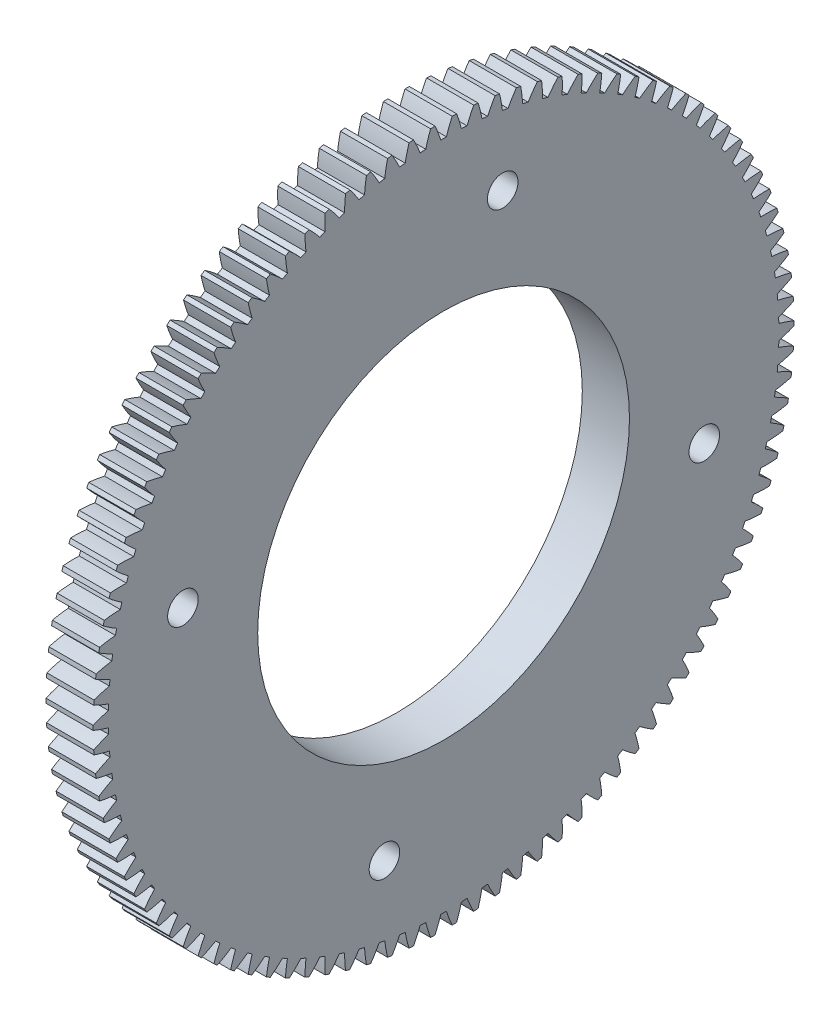
SolidWorks part; units mm, degrees
ref_plane "Plane1" through (0, 0, 0) normal (0, 0, 1) x (1, 0, 0)
ref_plane "Plane2" through (0, 0, 0) normal (0, 1, 0) x (1, 0, 0)
ref_plane "Plane3" through (0, 0, 0) normal (1, 0, 0) x (0, 0, -1)
sketch "HoldingSke" plane through (0, 0, 0) normal (0, 1, 0) x (1, 0, 0)
  line L0 (0, 0) -> (-105.6191, -496.899)
  line L1 (-15, 0) -> (100, 0) construction
  line L2 (0, 0) -> (-2.1039, 2.3779)
  line L3 (0, 0) -> (-11.863, 4.5341)
  line L4 (0, 0) -> (-1.7955, 8.4473)
  line L5 (0, 0) -> (-47.5972, -17.7524)
  line L6 (0, 0) -> (-7.3695, -4.9722)
  line L7 (-2.1039, 2.3779) -> (8.8308, 51.9871)
  line L8 (-76.2, 54.61) -> (-75.184, 54.61)
  line L9 (-71.009, 38.7566) -> (-53.1078, 45.2721)
  line L10 (-76.2, 71.12) -> (104.1128, 71.12)
  line L11 (0, 0) -> (-8.89, 0)
  line L12 (-76.2, 101.6) -> (-76.1492, 101.6)
  line L13 (24.9733, 27.94) -> (52.9518, 28.4284)
  line L14 (24.9733, 27.94) -> (25.0241, 27.9398)
  line L15 (24.9733, 27.94) -> (100.4021, 29.52)
  circle A0 centre (0, 0) radius 0.3969
  circle A1 centre (0, 0) radius 38.1
  circle A2 centre (0, 0) radius 38.1
  circle A3 centre (0, 0) radius 0.3969
  dimension "MHD" = 76.2
  dimension "Hub_dia" = 76.2
  dimension "Bore" = 0.7937
  dimension "MBD" = 0.7937
  dimension "Num_teeth" = 102
  dimension "Pitch" = 508
  dimension "Overall_len" = 50.8
  dimension "Show_teeth" = 102
  dimension "Thickness" = 8.89
  dimension "OAL" = 50.8001
  dimension "T_dim" = 1.016
  dimension "Ap" = 20
  dimension "H" = 19.05
  dimension "Pitch_radius" = 180.3128
  dimension "Width" = 8.89
  dimension "Backlash" = 0.0508
  dimension "Addendum_fac" = 1
  dimension "Dedendum_fac" = 1.2
  dimension "Clearance_fac" = 0.2
  dimension "Dedendum_add" = 0.0508
sketch "BasProSke" plane through (0, 0, 0) normal (0, 1, 0) x (1, 0, 0)
  line L0 (-10, 0) -> (60, 0) construction
  line L1 (0, 0) -> (0, 66.04)
  line L2 (0, 0) -> (8.89, 0)
  line L3 (8.89, 0) -> (8.89, 66.04)
  line L4 (8.89, 66.04) -> (0, 66.04)
  dimension "Thickness" = 8.89
  dimension "Diameter" = 132.08
revolve "Base-Revolve" add sketch "BasProSke" angle 360 about L0
sketch "TooCutSke" plane through (0, 0, 0) normal (1, 0, 0) x (0, 0, -1)
  line L1 (0, 0) -> (0, 107) construction
  line L2 (0, 0) -> (-1.0863, 64.7609) construction
  line L3 (0, 0) -> (-3.9888, 129.4658) construction
  line L4 (-1.0863, 64.7609) -> (-1.9944, 64.7329) construction
  arc A0 (0.5348, 63.1929) -> (-0.5348, 63.1929) centre (0, 0) ccw
  arc A1 (1.6252, 66.0454) -> (-1.6252, 66.0454) centre (0, 0) ccw
  circle A2 centre (0, 0) radius 64.77 construction
  circle A3 centre (0, 0) radius 60.8639 construction
  arc A4 (-0.5348, 63.1929) -> (-1.6252, 66.0454) centre (-25.2381, 55.3846) ccw
  arc A5 (1.6252, 66.0454) -> (0.5348, 63.1929) centre (25.2381, 55.3846) ccw
  dimension "Root_dia" = 126.3904
  dimension "Overcut_dia" = 132.1308
  dimension "Pitch_dia" = 129.54
  dimension "Base_dia" = 121.7278
  dimension "Flank_rad" = 25.908
  dimension "Half_ang" = 1.765
  dimension "Half_CT" = 0.9085
extrude "ToothCut" cut sketch "TooCutSke" along normal through all
fillet "Breaks" [suppressed] radius 0.0254 tangent propagation no
fillet "RootFillets" [suppressed] radius 0.3048
pattern_circular "TeethCuts" count 102 every 3.529 about axis through (-10, 0, 0) along (1, 0, 0) of "ToothCut", "RootFillets", "Breaks"
sketch "HubNeaOneSke" plane through (0, 0, 0) normal (-1, 0, 0) x (0, 0, 1)
  circle A0 centre (0, 0) radius 38.1
  dimension "Diameter" = 76.2
extrude "HubNearOne" [suppressed] add sketch "HubNeaOneSke" along normal blind 41.9101
sketch "HubNeaBotSke" plane through (0, 0, 0) normal (-1, 0, 0) x (0, 0, 1)
  circle A0 centre (0, 0) radius 38.1
  dimension "Diameter" = 76.2
extrude "HubNearBoth" [suppressed] add sketch "HubNeaBotSke" along normal blind 20.955
ref_plane "FarPln" through (8.89, 0, 0) normal (1, 0, 0) x (0, 0, -1)
sketch "HubFarSke" plane through (8.89, 0, 0) normal (1, 0, 0) x (0, 0, -1)
  circle A0 centre (0, 0) radius 38.1
  dimension "Diameter" = 76.2
extrude "HubFar" [suppressed] add sketch "HubFarSke" along normal blind 20.955
sketch "BorSke" plane through (0, 0, 0) normal (1, 0, 0) x (0, 0, -1)
  circle A0 centre (0, 0) radius 0.3969
  dimension "Diameter" = 0.7937
extrude "Bore" cut sketch "BorSke" along normal mid plane 101.6001
sketch "KeySke" plane through (0, 0, 0) normal (1, 0, 0) x (0, 0, -1)
  line L0 (-0.127, 0) -> (-0.127, 0.6191)
  line L1 (-0.127, 0.6191) -> (0.127, 0.6191)
  line L2 (0.127, 0.6191) -> (0.127, 0)
  line L3 (0, 0) -> (0, 34) construction
  line L4 (-0.127, 0) -> (0.127, 0)
  dimension "Offset" = 0.6191
  dimension "Width" = 0.254
extrude "Keyway" [suppressed] cut sketch "KeySke" along normal mid plane 101.6001
pattern_circular "Keyway2" [suppressed] count 2 every 90 about axis through (-10, 0, 0) along (1, 0, 0) reverse direction yes
sketch "Sketch1" plane through (8.89, 0, 0) normal (1, 0, 0) x (0, 0, -1)
  circle A0 centre (0, 0) radius 35.0348
extrude "Cut-Extrude1" cut sketch "Sketch1" against normal through all
sketch "Sketch2" plane through (8.89, 0, 0) normal (1, 0, 0) x (0, 0, -1)
  circle A0 centre (11.1435, 49.127) radius 2.8796
  circle A1 centre (49.127, -11.1435) radius 2.8796
  circle A2 centre (-11.1435, -49.127) radius 2.8796
  circle A3 centre (-49.127, 11.1435) radius 2.8796
  point P11 (0, 0)
  dimension "D1" = 4
extrude "Cut-Extrude2" cut sketch "Sketch2" against normal through all
equation "' \"Pitch@HoldingSke\" = 4"
equation "' \"Num_teeth@HoldingSke\" = 12"
equation "' \"Ap@HoldingSke\" =  20"
equation "' \"Ap@HoldingSke\" = 20"
equation "' \"Width@HoldingSke\" = 0.5"
equation "' \"Hub_dia@HoldingSke\"= 1"
equation "' \"Hub_dia@HoldingSke\" = 1"
equation "' \"Overall_len@HoldingSke\" = 1.0"
equation "' \"Bore@HoldingSke\" = 0.75"
equation "' \"T_dim@HoldingSke\" = 0.85"
equation "' \"Width@KeySke\" = 0.25"
equation "' \"Show_teeth@HoldingSke\" = 13"
equation "' \"Backlash@HoldingSke\" = 0.009"
equation "' \"Addendum_fac@HoldingSke\" = 1.0"
equation "' \"Dedendum_fac@HoldingSke\" = 1.25"
equation "' \"Dedendum_add@HoldingSke\" = 0.00005"
equation "' \"Clearance_fac@HoldingSke\" = 0.25"
equation "' \"Pitch@HoldingSke\" = 0.5"
equation "' \"Num_teeth@HoldingSke\" = 23"
equation "' \"Show_teeth@HoldingSke\" = 23"
equation "' \"Backlash@HoldingSke\" = 0.0375"
equation "\"Overcut_dia@TooCutSke\" = (\"Num_teeth@HoldingSke\" + 2 * \"Addendum_fac@HoldingSke\") / \"Pitch@HoldingSke\" + 0.002"
equation "\"Pitch_dia@TooCutSke\" = \"Num_teeth@HoldingSke\" / \"Pitch@HoldingSke\""
equation "\"Base_dia@TooCutSke\" = \"Num_teeth@HoldingSke\" / \"Pitch@HoldingSke\" * cos((\"Ap@HoldingSke\"  * 3.14159265 / 180))"
equation "\"Root_dia@TooCutSke\" = (\"Num_teeth@HoldingSke\" + 2) / \"Pitch@HoldingSke\" - 2 * (\"Addendum_fac@HoldingSke\" + \"Dedendum_fac@HoldingSke\") / \"Pitch@HoldingSke\" - \"Dedendum_add@HoldingSke\" * 2"
equation "\"Half_ang@TooCutSke\" = 180 / \"Num_teeth@HoldingSke\""
equation "\"Half_CT@TooCutSke\" = \"Num_teeth@HoldingSke\" / \"Pitch@HoldingSke\" * sin((3.14159265 / 2 / \"Num_teeth@HoldingSke\")) / 2 - 7 * \"Backlash@HoldingSke\" / 4"
equation "\"Flank_rad@TooCutSke\" = \"Num_teeth@HoldingSke\" / \"Pitch@HoldingSke\" / 5"
equation "\"Radius@RootFillets\" = \"Clearance_fac@HoldingSke\" / \"Pitch@HoldingSke\" + \"Dedendum_add@HoldingSke\""
equation "\"Break_rad@Breaks\" = 0.02 / \"Pitch@HoldingSke\""
equation "\"Thickness@HoldingSke\" = \"Width@HoldingSke\""
equation "\"OAL@HoldingSke\" = \"Thickness@HoldingSke\""
equation "\"MHD@HoldingSke\" = (\"Num_teeth@HoldingSke\" + 2) / \"Pitch@HoldingSke\" - 2 * (\"Addendum_fac@HoldingSke\" + \"Dedendum_fac@HoldingSke\")  / \"Pitch@HoldingSke\" - \"Dedendum_add@HoldingSke\" * 2"
equation "\"MBD@HoldingSke\" = (\"Num_teeth@HoldingSke\" + 2) / \"Pitch@HoldingSke\" - 2 * (\"Addendum_fac@HoldingSke\" + \"Dedendum_fac@HoldingSke\")  / \"Pitch@HoldingSke\" - \"Dedendum_add@HoldingSke\" * 2 - 0.002"
equation "\"MHD@HoldingSke\" = ((sgn( \"MHD@HoldingSke\" - \"Hub_dia@HoldingSke\" )-1)*( \"MHD@HoldingSke\" - \"Hub_dia@HoldingSke\" ))/-2+ \"Hub_dia@HoldingSke\""
equation "\"MBD@HoldingSke\" = ((sgn( \"MBD@HoldingSke\" - \"Bore@HoldingSke\" )-1)*( \"MBD@HoldingSke\" - \"Bore@HoldingSke\" ))/-2+ \"Bore@HoldingSke\""
equation "\"OAL@HoldingSke\" = ((sgn( \"OAL@HoldingSke\" - \"Overall_len@HoldingSke\" )+1)*( \"OAL@HoldingSke\" - \"Overall_len@HoldingSke\" ))/2 + \"Overall_len@HoldingSke\" + 0.000002"
equation "\"Num_teeth@TeethCuts\" = int( \"Show_teeth@HoldingSke\" ) + 1"
equation "\"Num_teeth@TeethCuts\" = ((sgn( \"Num_teeth@TeethCuts\" - \"Num_teeth@HoldingSke\" )-1)*( \"Num_teeth@TeethCuts\" - \"Num_teeth@HoldingSke\" ))/-2+ \"Num_teeth@HoldingSke\""
equation "\"Num_teeth@TeethCuts\" = ((sgn( \"Num_teeth@TeethCuts\" - 2.0)+1)*( \"Num_teeth@TeethCuts\" - 2.0))/2 +2.0"
equation "\"Angle@TeethCuts\" = 360.0 / \"Num_teeth@HoldingSke\""
equation "\"Diameter@BasProSke\" = (\"Num_teeth@HoldingSke\" + 2 * \"Addendum_fac@HoldingSke\") / \"Pitch@HoldingSke\""
equation "\"Thickness@BasProSke\"  = \"Thickness@HoldingSke\""
equation "' \"Fillet_rad@BasProSke\" =  \"Thickness@HoldingSke\" * 0.05"
equation "' \"Fillet_rad@BasProSke\" = \"Thickness@HoldingSke\" * 0.05"
equation "\"MHD@HoldingSke\" = ((sgn( \"MHD@HoldingSke\" - \"Root_dia@TooCutSke\" )-1)*( \"MHD@HoldingSke\" - \"Root_dia@TooCutSke\" ))/-2+ \"Root_dia@TooCutSke\""
equation "\"Diameter@HubNeaOneSke\" = \"MHD@HoldingSke\""
equation "\"Length@HubNearOne\" = \"OAL@HoldingSke\" - \"Thickness@BasProSke\""
equation "\"Diameter@HubNeaBotSke\" = \"MHD@HoldingSke\""
equation "\"Length@HubNearBoth\" = ( \"OAL@HoldingSke\" - \"Thickness@BasProSke\" ) / 2.0"
equation "\"Thickness@FarPln\" = \"Thickness@BasProSke\""
equation "\"Diameter@HubFarSke\" = \"MHD@HoldingSke\""
equation "\"Length@HubFar\" = ( \"OAL@HoldingSke\" - \"Thickness@BasProSke\" ) / 2.0"
equation "\"Diameter@BorSke\" = \"MBD@HoldingSke\""
equation "\"D1@Bore\" = \"OAL@HoldingSke\" * 2.0"
equation "\"D1@Keyway\" = \"OAL@HoldingSke\" * 2.0"
equation "\"Offset@KeySke\" = \"T_dim@HoldingSke\" - \"MBD@HoldingSke\" / 2.0"
